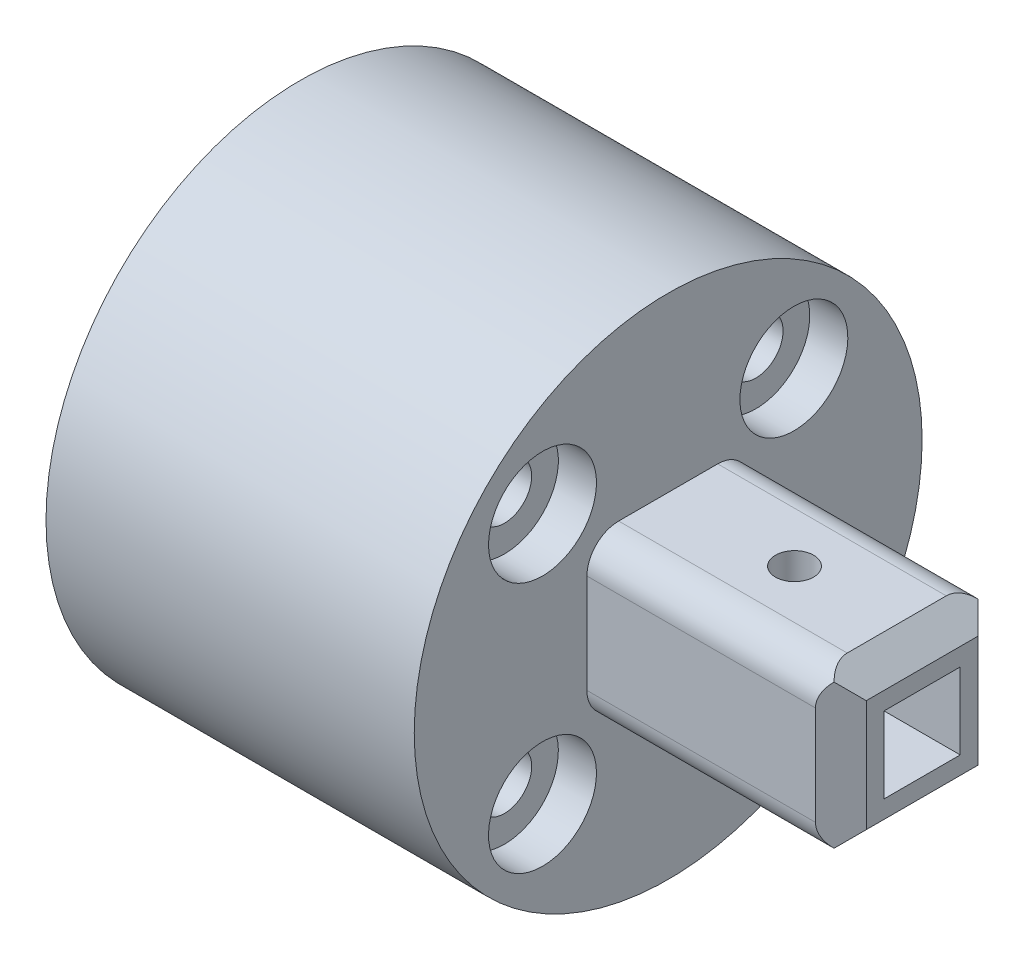
SolidWorks part; units mm, degrees
ref_plane "前视基准面" through (0, 0, 0) normal (0, 0, 1) x (1, 0, 0)
ref_plane "上视基准面" through (0, 0, 0) normal (0, 1, 0) x (1, 0, 0)
ref_plane "右视基准面" through (0, 0, 0) normal (1, 0, 0) x (0, 0, -1)
sketch "草图1" plane through (0, 0, 0) normal (1, 0, 0) x (0, 0, -1)
  circle A0 centre (0, 0) radius 20
  dimension "D1" = 40
extrude "凸台-拉伸1" add sketch "草图1" along normal blind 10
sketch "草图2" plane through (0, 0, 0) normal (-1, 0, 0) x (0, 0, 1)
  line L1 (-7.5, -15.25) -> (7.5, -15.25)
  line L2 (-7.5, -15.25) -> (-7.5, 15.25)
  line L3 (-7.5, 15.25) -> (7.5, 15.25)
  line L4 (7.5, -15.25) -> (7.5, 15.25)
  line L5 (-7.5, -15.25) -> (7.5, 15.25) construction
  line L6 (-7.5, 15.25) -> (7.5, -15.25) construction
  point P0 (0, 0)
  dimension "D1" = 15
  dimension "D2" = 30.5
extrude "切除-拉伸1" cut sketch "草图2" against normal blind 4
sketch "草图3" plane through (4, 0, 0) normal (-1, 0, 0) x (0, 0, 1)
  circle A0 centre (0, 0) radius 8.75
  dimension "D1" = 17.5
extrude "切除-拉伸2" cut sketch "草图3" along normal blind 4
sketch "草图4" plane through (0, 0, 0) normal (-1, 0, 0) x (0, 0, 1)
  line L1 (-9, -16) -> (9, -16)
  line L2 (-9, -16) -> (-9, 16)
  line L3 (-9, 16) -> (9, 16)
  line L4 (9, -16) -> (9, 16)
  line L5 (-9, -16) -> (9, 16) construction
  line L6 (-9, 16) -> (9, -16) construction
  circle A0 centre (0, 0) radius 20
  dimension "D3" = 40
  dimension "D1" = 32
  dimension "D2" = 18
extrude "凸台-拉伸2" add sketch "草图4" along normal blind 19
fillet "圆角1" radius 3 4 edges at (-9.5, -16, -9) (-9.5, -16, 9) (-9.5, 16, -9) (-9.5, 16, 9)
sketch "草图5" plane through (-19, 0, 0) normal (-1, 0, 0) x (0, 0, 1)
  line L0 (-6, -16) -> (6, -16) construction
  line L1 (6, 16) -> (-6, 16) construction
  circle A0 centre (0, -16) radius 2.5
  circle A1 centre (0, 16) radius 2.5
  dimension "D1" = 5
  dimension "D2" = 5
extrude "切除-拉伸3" cut sketch "草图5" against normal blind 20
fillet "圆角2" radius 3 4 edges at (-9.5, -16, -2.5) (-9.5, -16, 2.5) (-9.5, 16, -2.5) (-9.5, 16, 2.5)
sketch "草图6" plane through (10, 0, 0) normal (1, 0, 0) x (0, 0, -1)
  line L0 (0, 0) -> (20, 0) construction
  line L1 (0, 0) -> (18.216, -18.216) construction
  circle A0 centre (0, 0) radius 14 construction
  circle A2 centre (9.8995, -9.8995) radius 2.15
  circle A3 centre (0, 0) radius 14 construction
  circle A4 centre (-9.8995, -9.8995) radius 2.15
  circle A5 centre (0, 0) radius 14 construction
  circle A6 centre (-9.8995, 9.8995) radius 2.15
  circle A7 centre (0, 0) radius 14 construction
  circle A8 centre (9.8995, 9.8995) radius 2.15
  point P21 (0, 0)
  dimension "D1" = 28
  dimension "D3" = 4.3
  dimension "D2" = 45
  dimension "D4" = 4
extrude "切除-拉伸4" cut sketch "草图6" against normal blind 43
fillet "圆角3" radius 1 8 edges at (-9.5, -11.8523, 9) (-9.5, -7.9467, 9) (-9.5, -11.8523, -9) (-9.5, -7.9467, -9) (-9.5, 7.9467, -9) (-9.5, 11.8523, -9) (-9.5, 7.9467, 9) (-9.5, 11.8523, 9)
sketch "草图7" plane through (10, 0, 0) normal (1, 0, 0) x (0, 0, -1)
  circle A0 centre (9.8995, -9.8995) radius 4.25
  dimension "D1" = 8.5
extrude "切除-拉伸5" cut sketch "草图7" against normal blind 3
pattern_circular "阵列(圆周)1" count 4 over 360 about axis through (10, 0, 0) along (1, 0, 0) of "切除-拉伸5"
sketch "草图8" plane through (10, 0, 0) normal (1, 0, 0) x (0, 0, -1)
  line L1 (6.4, -6.4) -> (-6.4, -6.4)
  line L2 (6.4, -6.4) -> (6.4, 6.4)
  line L3 (6.4, 6.4) -> (-6.4, 6.4)
  line L4 (-6.4, -6.4) -> (-6.4, 6.4)
  line L5 (6.4, -6.4) -> (-6.4, 6.4) construction
  line L6 (6.4, 6.4) -> (-6.4, -6.4) construction
  point P0 (0, 0)
  dimension "D1" = 12.8
  dimension "D2" = 12.8
extrude "凸台-拉伸3" add sketch "草图8" along normal blind 20
sketch "草图9" plane through (30, 0, 0) normal (1, 0, 0) x (0, 0, -1)
  line L1 (3, -3) -> (-3, -3)
  line L2 (3, -3) -> (3, 3)
  line L3 (3, 3) -> (-3, 3)
  line L4 (-3, -3) -> (-3, 3)
  line L5 (3, -3) -> (-3, 3) construction
  line L6 (3, 3) -> (-3, -3) construction
  point P0 (0, 0)
  dimension "D1" = 6
  dimension "D2" = 6
extrude "切除-拉伸6" cut sketch "草图9" against normal blind 35
sketch "草图10" plane through (1, 0, 0) normal (-1, 0, 0) x (0, 0, 1)
  line L0 (-3, 3) -> (3, 3) construction
  line L1 (-1.5, 3) -> (1.5, 3)
  line L2 (-1.5, 3) -> (-1.5, 18)
  line L3 (-1.5, 18) -> (1.5, 18)
  line L4 (1.5, 3) -> (1.5, 18)
  arc A0 (2.3848, 15.25) -> (-2.3848, 15.25) centre (0, 16) ccw construction
  dimension "D1" = 3
  dimension "D2" = 1.5
extrude "切除-拉伸7" cut sketch "草图10" against normal blind 5
sketch "草图11" plane through (1, 0, 0) normal (-1, 0, 0) x (0, 0, 1)
  circle A0 centre (0, 16) radius 2.5
  dimension "D1" = 5
extrude "切除-拉伸8" cut sketch "草图11" against normal blind 5
sketch "草图12" plane through (0, -6.4, 0) normal (0, -1, 0) x (1, 0, 0)
  line L0 (10, 6.4) -> (10, -6.4) construction
  line L1 (30, 6.4) -> (10, 6.4) construction
  circle A0 centre (20, 0.05) radius 1.5
  dimension "D1" = 3
  dimension "D2" = 10
  dimension "D3" = 6.35
extrude "切除-拉伸9" cut sketch "草图12" against normal blind 17
chamfer "倒角1" distance 2 angle 45 4 edges at (30, 0, 6.4) (30, 6.4, 0) (30, 0, -6.4) (30, -6.4, 0)
fillet "圆角4" radius 3 1 edges at (6, 3, 0)
fillet "圆角5" radius 2.5 4 edges at (19, -6.4, -6.4) (19, -6.4, 6.4) (19, 6.4, 6.4) (19, 6.4, -6.4)
